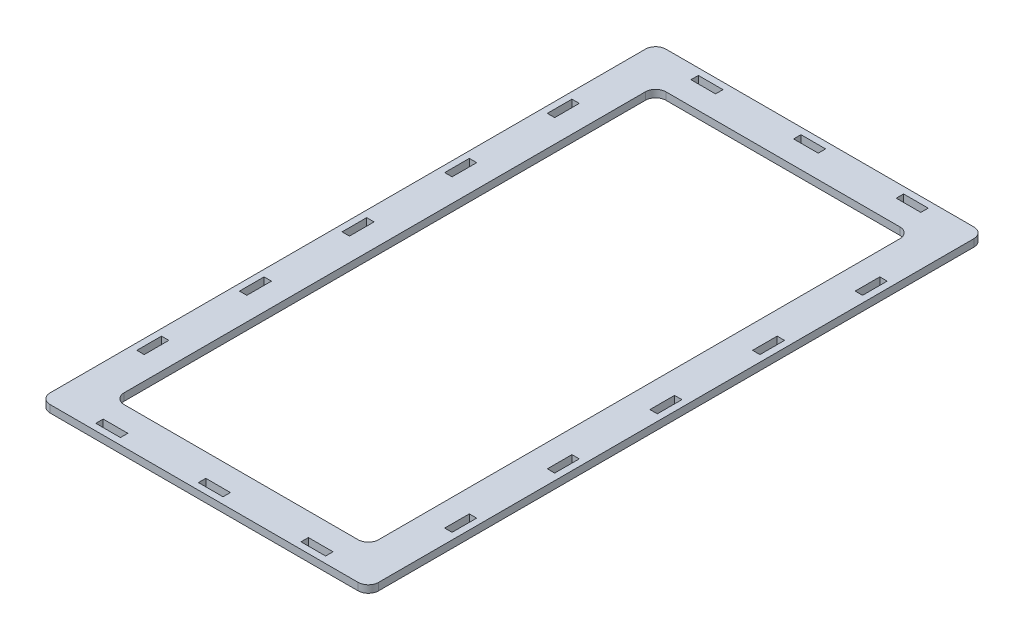
SolidWorks part; units mm, degrees
ref_plane "前视基准面" through (0, 0, 0) normal (0, 0, 1) x (1, 0, 0)
ref_plane "上视基准面" through (0, 0, 0) normal (0, 1, 0) x (1, 0, 0)
ref_plane "右视基准面" through (0, 0, 0) normal (1, 0, 0) x (0, 0, -1)
other "Configuration Table"
sketch "草图1" plane through (0, 0, 0) normal (0, 1, 0) x (1, 0, 0)
  line L1 (-400, 750) -> (400, 750)
  line L2 (-400, 750) -> (-400, -750)
  line L3 (-400, -750) -> (400, -750)
  line L4 (400, 750) -> (400, -750)
  line L5 (-384, -470) -> (-366, -470)
  line L6 (-384, -470) -> (-384, -530)
  line L7 (-384, -530) -> (-366, -530)
  line L8 (-366, -470) -> (-366, -530)
  line L9 (-280, -734) -> (-220, -734)
  line L10 (-280, -734) -> (-280, -716)
  line L11 (-280, -716) -> (-220, -716)
  line L12 (-220, -734) -> (-220, -716)
  line L13 (-310, 660) -> (310, 660)
  line L14 (-310, 660) -> (-310, -660)
  line L15 (-310, -660) -> (310, -660)
  line L16 (310, 660) -> (310, -660)
  point P4 (-400, 0)
  point P6 (0, -750)
  point P11 (-384, -500)
  point P20 (0, -660)
  point P21 (-310, 0)
  point P23 (-220, -725)
  point P24 (-375, -530)
  dimension "D1" = 800
  dimension "D2" = 1500
  dimension "D3" = 250
  dimension "D4" = 18
  dimension "D5" = 60
  dimension "D6" = 90
  dimension "D7" = 90
  dimension "D8" = 60
  dimension "D9" = 18
  dimension "D10" = 120
  dimension "D11" = 25
  dimension "D12" = 25
extrude "凸台-拉伸1" add sketch "草图1" along normal blind 18 contours L2 L3 L4 L1 | L14 L15 L16 L13
extrude "切除-拉伸1" cut sketch "草图1<5>" along normal through all contours L7 L8 L5 L6
sketch "草图1<5>" plane through (0, 0, 0) normal (0, 1, 0) x (1, 0, 0) same geometry as "草图1"
pattern_linear "阵列(线性)1" count 5 spacing 250 along (0, 0, -1) of "切除-拉伸1"
mirror "镜向1" about plane through (0, 0, 0) normal (1, 0, 0) of "切除-拉伸1", "阵列(线性)1"
extrude "切除-拉伸2" cut sketch "草图1<4>" along normal through all contours L12 L11 L10 L9
sketch "草图1<4>" plane through (0, 0, 0) normal (0, 1, 0) x (1, 0, 0) same geometry as "草图1"
pattern_linear "阵列(线性)2" count 3 spacing 250 along (1, 0, 0) of "切除-拉伸2"
mirror "镜向2" about plane through (0, 0, 0) normal (0, 0, 1) of "阵列(线性)2", "切除-拉伸2"
fillet "圆角1" radius 25 4 edges at (-400, 9, -750) (400, 9, -750) (400, 9, 750) (-400, 9, 750)
fillet "圆角2" radius 25 4 edges at (-310, 9, -660) (310, 9, -660) (310, 9, 660) (-310, 9, 660)
